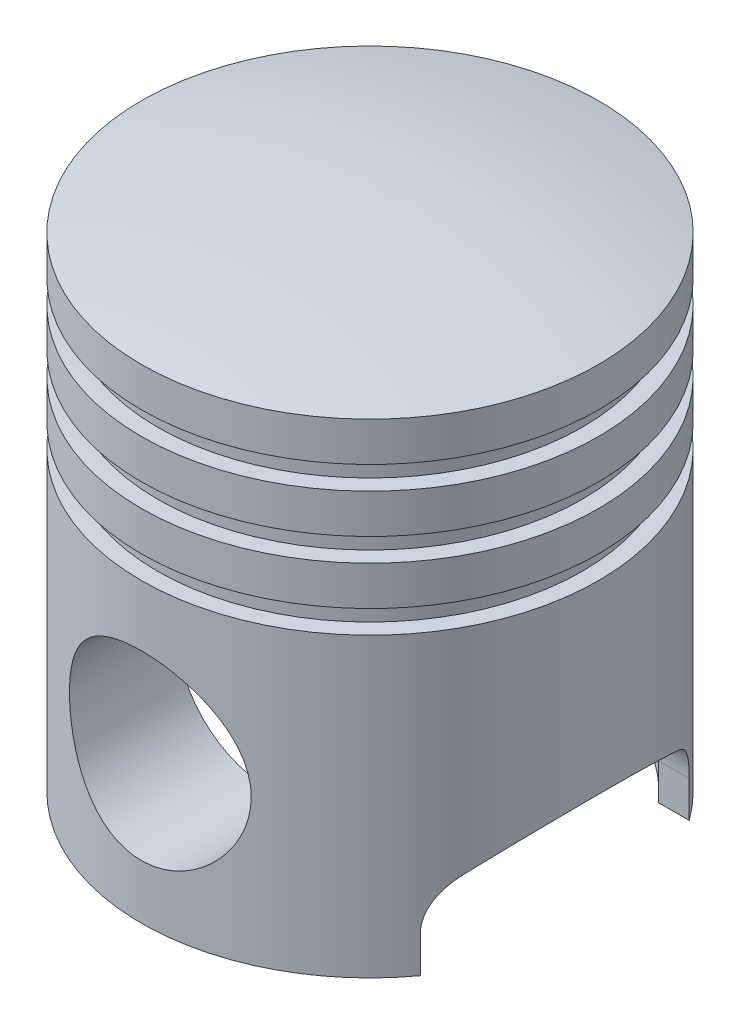
SolidWorks part; units mm, degrees
ref_plane "Front Plane" through (0, 0, 0) normal (0, 0, 1) x (1, 0, 0)
ref_plane "Top Plane" through (0, 0, 0) normal (0, 1, 0) x (1, 0, 0)
ref_plane "Right Plane" through (0, 0, 0) normal (1, 0, 0) x (0, 0, -1)
sketch "Sketch1" plane through (0, 0, 0) normal (0, 1, 0) x (1, 0, 0)
  circle A0 centre (0, 0) radius 1079.5
  dimension "D1" = 2159
extrude "Boss-Extrude1" add sketch "Sketch1" along normal blind 2286
sketch "Sketch2" plane through (0, 2286, 0) normal (0, 1, 0) x (1, 0, 0)
  circle A0 centre (0, 0) radius 1003.3
  dimension "D1" = 2006.6
extrude "Cut-Extrude1" cut sketch "Sketch2" against normal blind 109.22 from offset 185.42 flip side to cut offset against normal yes
pattern_linear "LPattern2" count 3 spacing 294.64 along (0, -1, 0) of "Cut-Extrude1"
dome "Dome1" faces to dome 1 distance 127 reverse direction no elliptical dome no face at (0, 2286, 1079.5) parameters "D1"=127
sketch "Sketch3" plane through (0, 0, 0) normal (0, -1, 0) x (1, 0, 0)
  circle A0 centre (0, 0) radius 965.2
  dimension "D1" = 1930.4
extrude "Cut-Extrude2" cut sketch "Sketch3" against normal blind 2159
sketch "Sketch4" plane through (0, 0, 0) normal (0, 0, 1) x (1, 0, 0)
  line L0 (-1079.5, 0) -> (1079.5, 0) construction
  circle A0 centre (0, 685.8) radius 429.26
  dimension "D1" = 858.52
  dimension "D2" = 685.8
extrude "Cut-Extrude3" cut sketch "Sketch4" against normal through all both and the other way through all
sketch "Sketch7" plane through (0, 0, 0) normal (1, 0, 0) x (0, 0, -1)
  line L0 (0, 0) -> (0, 597.2988) construction
  line L2 (-1079.5, 0) -> (1079.5, 0) construction
  line L8 (-635, 304.8) -> (-635, 0)
  line L9 (-635, 0) -> (635, 0)
  line L10 (635, 304.8) -> (635, 0)
  arc A0 (-635, 304.8) -> (635, 304.8) centre (0, -488.3147) cw
  point P2 (0, 152.4)
  dimension "D3" = 1016
  dimension "D1" = 1270
  dimension "D2" = 304.8
extrude "Cut-Extrude5" cut sketch "Sketch7" against normal through all both and the other way through all
fillet "Fillet1" radius 254 4 edges at (799.9412, 304.8, 635) (-799.9412, 304.8, 635) (-799.9412, 304.8, -635) (799.9412, 304.8, -635)
sketch "Sketch8" plane through (0, 0, 0) normal (0, 0, 1) x (1, 0, 0)
  circle A2 centre (0, 685.8) radius 429.26 construction
  circle A3 centre (0, 685.8) radius 429.26
  circle A4 centre (0, 685.8) radius 571.5
  dimension "D1" = 1143
extrude "Boss-Extrude2" add sketch "Sketch8" along normal up to next from offset 482.6
mirror "Mirror1" about plane through (0, 0, 0) normal (0, 0, 1) of "Boss-Extrude2"
